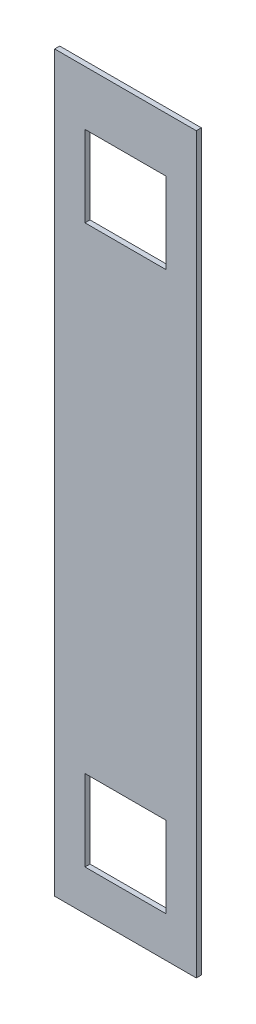
SolidWorks part; units mm, degrees
material "Oak"
ref_plane "Front Plane" through (0, 0, 0) normal (0, 0, 1) x (1, 0, 0)
ref_plane "Top Plane" through (0, 0, 0) normal (0, 1, 0) x (1, 0, 0)
ref_plane "Right Plane" through (0, 0, 0) normal (1, 0, 0) x (0, 0, -1)
sketch "Sketch1" plane through (0, 0, 0) normal (0, 0, 1) x (1, 0, 0)
  line L1 (-88.9, -460.375) -> (88.9, -460.375)
  line L2 (-88.9, -460.375) -> (-88.9, 460.375)
  line L3 (-88.9, 460.375) -> (88.9, 460.375)
  line L4 (88.9, -460.375) -> (88.9, 460.375)
  line L5 (-88.9, -460.375) -> (88.9, 460.375) construction
  line L6 (-88.9, 460.375) -> (88.9, -460.375) construction
  point P0 (0, 0)
  dimension "D1" = 920.75
  dimension "D2" = 177.8
extrude "Boss-Extrude1" add sketch "Sketch1" along normal blind 6.35
sketch "Sketch2" plane through (0, 0, 0) normal (0, 0, -1) x (-1, 0, 0)
  line L0 (-50.8, -409.575) -> (-88.9, -409.575) construction
  line L1 (-50.8, -307.975) -> (50.8, -307.975)
  line L2 (-50.8, -307.975) -> (-50.8, -409.575)
  line L3 (-50.8, -409.575) -> (50.8, -409.575)
  line L4 (50.8, -307.975) -> (50.8, -409.575)
  line L5 (-88.9, -460.375) -> (-88.9, 460.375) construction
  line L6 (50.8, -409.575) -> (88.9, -409.575) construction
  line L7 (88.9, 460.375) -> (88.9, -460.375) construction
  line L8 (88.9, -460.375) -> (-88.9, -460.375) construction
  line L9 (-50.8, 392.025) -> (-50.8, 290.425)
  line L10 (-50.8, 392.025) -> (50.8, 392.025)
  line L11 (50.8, 392.025) -> (50.8, 290.425)
  line L12 (-50.8, 290.425) -> (50.8, 290.425)
  point P12 (50.8, 274.1291)
  dimension "D1" = 101.6
  dimension "D2" = 50.8
  dimension "D3" = 101.6
  dimension "D5" = 700
  dimension "D4" = 2
extrude "Cut-Extrude1" cut sketch "Sketch2" against normal up to next
